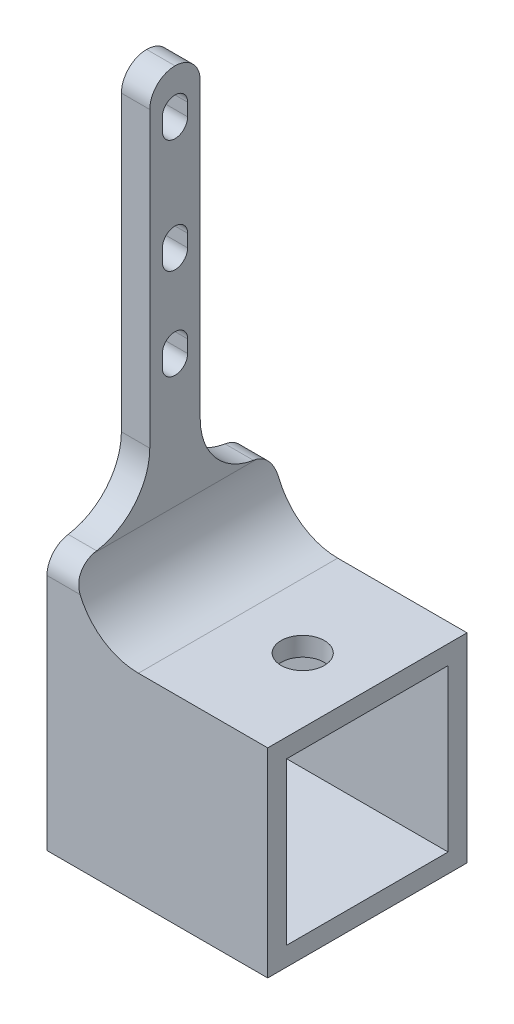
SolidWorks part; units mm, degrees
ref_plane "Front Plane" through (0, 0, 0) normal (0, 0, 1) x (1, 0, 0)
ref_plane "Top Plane" through (0, 0, 0) normal (0, 1, 0) x (1, 0, 0)
ref_plane "Right Plane" through (0, 0, 0) normal (1, 0, 0) x (0, 0, -1)
sketch "Sketch1" plane through (0, 0, 0) normal (1, 0, 0) x (0, 0, -1)
  line L1 (-12.8, -12.8) -> (12.8, -12.8)
  line L2 (-12.8, -12.8) -> (-12.8, 12.8)
  line L3 (-12.8, 12.8) -> (12.8, 12.8)
  line L4 (12.8, -12.8) -> (12.8, 12.8)
  line L5 (-12.8, -12.8) -> (12.8, 12.8) construction
  line L6 (-12.8, 12.8) -> (12.8, -12.8) construction
  line L7 (-15.8, -15.8) -> (15.8, -15.8)
  line L8 (-15.8, -15.8) -> (-15.8, 15.8)
  line L9 (-15.8, 15.8) -> (15.8, 15.8)
  line L10 (15.8, -15.8) -> (15.8, 15.8)
  line L11 (-15.8, -15.8) -> (15.8, 15.8) construction
  line L12 (-15.8, 15.8) -> (15.8, -15.8) construction
  point P0 (0, 0)
  point P6 (0, 0)
  dimension "D1" = 25.6
  dimension "D2" = 25.6
  dimension "D3" = 3
  dimension "D4" = 3
extrude "Boss-Extrude1" add sketch "Sketch1" along normal blind 35
sketch "Sketch2" plane through (0, 15.8, 0) normal (0, 1, 0) x (1, 0, 0)
  line L0 (35, -15.8) -> (0, -15.8) construction
  line L1 (0, 15.8) -> (4.5, 15.8)
  line L2 (0, 15.8) -> (0, -15.8)
  line L3 (0, -15.8) -> (4.5, -15.8)
  line L4 (4.5, 15.8) -> (4.5, -15.8)
  dimension "D1" = 4.5
extrude "Boss-Extrude2" add sketch "Sketch2" along normal blind 70.5
fillet "Fillet1" radius 10 1 edges at (4.5, 15.8, 0)
sketch "Sketch3" plane through (4.5, 0, 0) normal (1, 0, 0) x (0, 0, -1)
  line L0 (0, 45.8) -> (0, 47.8) construction
  line L1 (-2, 45.8) -> (-2, 47.8)
  line L2 (2, 45.8) -> (2, 47.8)
  line L3 (0, 60.3) -> (0, 62.3) construction
  line L4 (-2, 60.3) -> (-2, 62.3)
  line L5 (2, 60.3) -> (2, 62.3)
  line L6 (0, 78.3) -> (0, 80.3) construction
  line L7 (-2, 78.3) -> (-2, 80.3)
  line L8 (2, 78.3) -> (2, 80.3)
  line L9 (0, 80.3) -> (0, 45.8) construction
  line L10 (-15.8, 86.3) -> (15.8, 86.3) construction
  line L11 (15.8, 86.3) -> (15.8, 25.8) construction
  line L12 (-4, 25.8) -> (-4, 86.3)
  line L13 (-15.8, 25.8) -> (15.8, 25.8) construction
  line L14 (-4, 86.3) -> (-15.8, 86.3)
  line L15 (-15.8, 86.3) -> (-15.8, 25.8)
  line L16 (-15.8, 25.8) -> (-4, 25.8)
  line L17 (4, 25.8) -> (4, 86.3)
  line L18 (4, 86.3) -> (15.8, 86.3)
  line L19 (15.8, 86.3) -> (15.8, 25.8)
  line L20 (15.8, 25.8) -> (4, 25.8)
  arc A0 (-2, 45.8) -> (2, 45.8) centre (0, 45.8) ccw
  arc A1 (2, 47.8) -> (-2, 47.8) centre (0, 47.8) ccw
  arc A2 (-2, 60.3) -> (2, 60.3) centre (0, 60.3) ccw
  arc A3 (2, 62.3) -> (-2, 62.3) centre (0, 62.3) ccw
  arc A4 (-2, 78.3) -> (2, 78.3) centre (0, 78.3) ccw
  arc A5 (2, 80.3) -> (-2, 80.3) centre (0, 80.3) ccw
  point P2 (0, 46.8)
  point P7 (0, 61.3)
  point P14 (0, 79.3)
  point P21 (-11.7395, 52.5829)
  dimension "D2" = 2
  dimension "D5" = 6
  dimension "D1" = 18
  dimension "D3" = 2
  dimension "D4" = 2
  dimension "D6" = 15.8
  dimension "D7" = 4
  dimension "D8" = 4
extrude "Cut-Extrude1" cut sketch "Sketch3" against normal blind 13
fillet "Fillet2" radius 10 2 edges at (2.25, 25.8, -4) (2.25, 25.8, 4)
fillet "Fillet3" radius 4 1 edges at (2.25, 86.3, 4)
fillet "Fillet4" radius 4 1 edges at (2.25, 86.3, -4)
fillet "Fillet5" radius 4 1 edges at (2.25, 25.8, 15.8)
fillet "Fillet6" radius 4 1 edges at (2.25, 25.8, -15.8)
sketch "Sketch4" plane through (0, 15.8, 0) normal (0, 1, 0) x (1, 0, 0)
  line L1 (35, 15.8) -> (14.5, 15.8) construction
  line L3 (35, 15.8) -> (35, -15.8) construction
  circle A0 centre (24.75, 0) radius 3.43
  dimension "D1" = 6.86
  dimension "D2" = 15.8
  dimension "D3" = 10.25
extrude "Cut-Extrude2" cut sketch "Sketch4" against normal blind 13
sketch "Sketch6" plane through (0, -12.8, 0) normal (0, 1, 0) x (1, 0, 0)
  line L0 (35, -12.8) -> (0, -12.8) construction
  line L1 (0, 12.8) -> (4.5, 12.8)
  line L2 (0, 12.8) -> (0, -12.8)
  line L3 (0, -12.8) -> (4.5, -12.8)
  line L4 (4.5, 12.8) -> (4.5, -12.8)
  dimension "D1" = 4.5
extrude "Boss-Extrude3" add sketch "Sketch6" along normal blind 26
